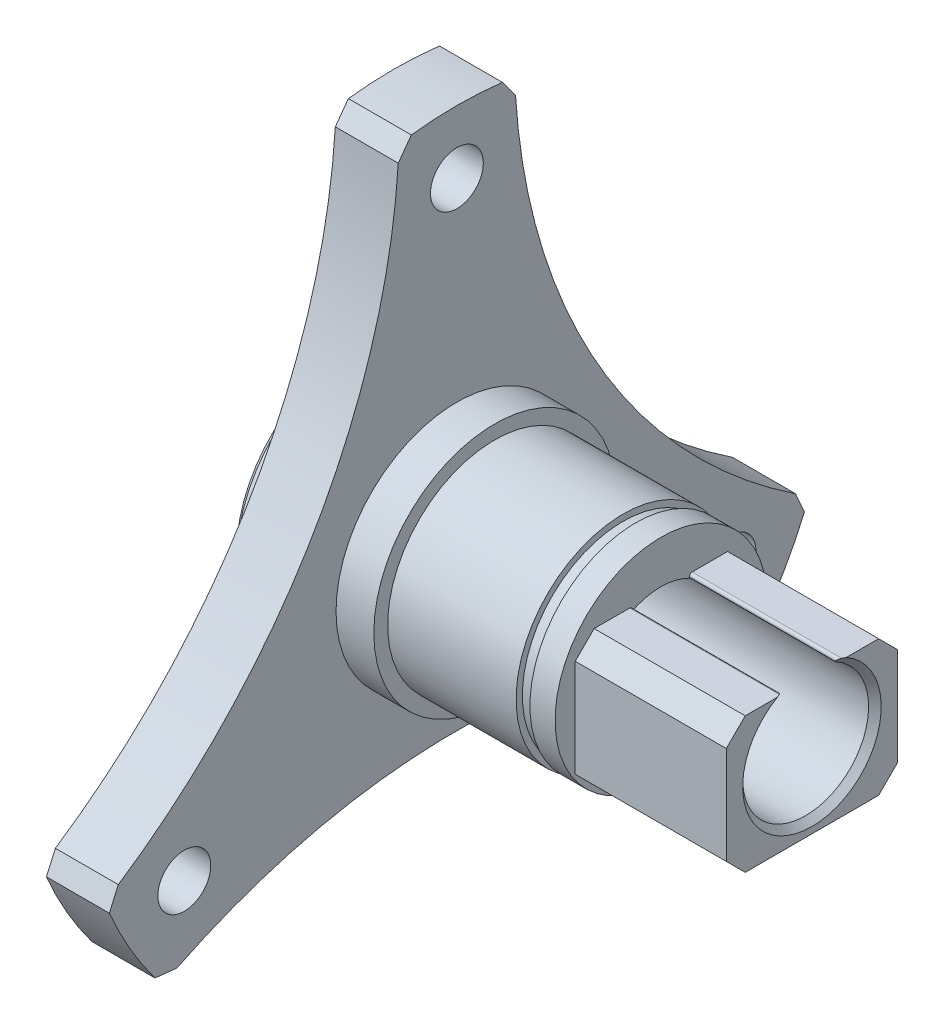
SolidWorks part; units mm, degrees
material "6061-T6 (SS)"
ref_plane "前视基准面" through (0, 0, 0) normal (0, 0, 1) x (1, 0, 0)
ref_plane "上视基准面" through (0, 0, 0) normal (0, 1, 0) x (1, 0, 0)
ref_plane "右视基准面" through (0, 0, 0) normal (1, 0, 0) x (0, 0, -1)
ref_axis "基准轴1" through (48.51, 0, 0) along (-1, 0, 0)
sketch "草图1" plane through (0, 0, 0) normal (0, 0, 1) x (1, 0, 0)
  line L0 (0, 0) -> (0, 10)
  line L2 (3, 10) -> (3, 30)
  line L3 (3, 30) -> (8, 30)
  line L4 (8, 30) -> (8, 9.6)
  line L5 (8, 9.6) -> (11, 9.6)
  line L6 (11, 9.6) -> (11, 8.5)
  line L7 (11, 8.5) -> (21.2, 8.5)
  line L12 (21.2, 8.5) -> (21.2, 8)
  line L13 (21.2, 8) -> (22.2, 8)
  line L14 (22.2, 8) -> (22.2, 8.4)
  line L15 (22.2, 8.4) -> (24.2, 8.4)
  line L16 (24.2, 8.4) -> (24.2, 0)
  line L19 (24.2, 0) -> (0, 0)
  line L21 (0, 10) -> (3, 10)
  dimension "D1" = 8.5
  dimension "D2" = 9.6
  dimension "D7" = 10.2
  dimension "D8" = 3
  dimension "D9" = 5
  dimension "D10" = 30
  dimension "D11" = 10
  dimension "D13" = 3
  dimension "D16" = 8
  dimension "D17" = 1
  dimension "D18" = 8.4
  dimension "D19" = 2
revolve "旋转1" add sketch "草图1" angle 360 about L19
sketch "草图2" plane through (24.2, 0, 0) normal (1, 0, 0) x (0, 0, -1)
  circle A0 centre (0, 0) radius 5
  dimension "D1" = 10
extrude "切除-拉伸1" cut sketch "草图2" against normal through all
sketch "草图3" plane through (0, 0, 0) normal (-1, 0, 0) x (0, 0, 1)
  circle A0 centre (0, 0) radius 8
  dimension "D1" = 16
extrude "切除-拉伸2" cut sketch "草图3" against normal blind 8
chamfer "倒角1" distance 3 angle 30 1 edges at (8, 0, 5) first distance on face at (8, 0, 8)
sketch "草图5" plane through (3, 0, 0) normal (-1, 0, 0) x (0, 0, 1)
  circle A0 centre (0, 0) radius 25 construction
  circle A1 centre (0, 25) radius 2.5
  circle A2 centre (21.6506, -12.5) radius 2.5
  circle A3 centre (-21.6506, -12.5) radius 2.5
  point P12 (0, 0)
  dimension "D1" = 50
  dimension "D2" = 3
  dimension "D3" = 5
hole_wizard "M5 螺纹孔1" positions "3D草图1" profile "草图6" tap size "M5" standard "GB" end condition through all
sketch3d "3D草图1"
  point P0 (3, 25, 0)
  point P3 (3, -12.5, 21.6506)
  point P6 (3, -12.5, -21.6506)
sketch "草图6" plane through (3, 25, 0) normal (0, 1, 0) x (0, 0, 1)
  line L0 (0, 0) -> (0, 21.2)
  line L1 (0, 21.2) -> (2.1, 21.2)
  line L2 (2.1, 21.2) -> (2.1, 0)
  line L5 (2.1, 0) -> (0, 0)
  line L11 (0, -6.35) -> (0, 107.95) construction
  dimension "通孔螺纹孔钻头直径" = 4.2
  dimension "通孔螺纹孔钻头深度" = 21.2
cosmetic thread "孔螺蚊线1" parameters "D2"=5
cosmetic thread "孔螺蚊线2" parameters "D2"=5
cosmetic thread "孔螺蚊线3" parameters "D2"=5
sketch "草图4" plane through (3, 0, 0) normal (-1, 0, 0) x (0, 0, 1)
  line L0 (0, 0) -> (0, -63) construction
  arc A0 (-27.7102, -21.381) -> (27.7102, -21.381) centre (0, 0) ccw
  arc A1 (27.7102, -21.381) -> (-27.7102, -21.381) centre (0, -63) ccw
  dimension "D1" = 70
  dimension "D3" = 100
  dimension "D2" = 63
extrude "切除-拉伸3" cut sketch "草图4" against normal through all
pattern_circular "阵列(圆周)1" count 3 over 360 about axis through (48.51, 0, 0) along (-1, 0, 0) of "切除-拉伸3"
chamfer "倒角2" distance 1 angle 45 6 edges at (5.5, 29.6462, -4.594) (5.5, 29.6462, 4.594) (5.5, -10.8446, 27.9713) (5.5, -18.8016, 23.3773) (5.5, -18.8016, -23.3773) (5.5, -10.8446, -27.9713) first distance on face at (5.5, 29.8231, 0) first distance on face at (5.5, -14.9115, 25.8275) first distance on face at (5.5, -14.9115, -25.8275)
chamfer "倒角4" distance 0.5 angle 45 1 edges at (0, 0, -10)
sketch "草图7" plane through (24.2, 0, 0) normal (1, 0, 0) x (0, 0, -1)
  line L0 (0, 0) -> (0, 2.7252) construction
  line L1 (-6.8, -6) -> (6.8, -6)
  line L2 (-6.8, -6) -> (-6.8, 4.7697)
  line L3 (-6.8, 4.7697) -> (-1.5, 4.7697)
  line L4 (6.8, -6) -> (6.8, 4.7697)
  line L5 (1.5, 4.7697) -> (6.8, 4.7697)
  arc A0 (-1.5, 4.7697) -> (1.5, 4.7697) centre (0, 0) ccw
  dimension "D1" = 10
  dimension "D2" = 13.6
  dimension "D3" = 6
  dimension "D4" = 3
extrude "凸台-拉伸1" add sketch "草图7" along normal blind 12
chamfer "倒角5" distance 1.5 angle 45 4 edges at (30.2, -6, -6.8) (30.2, -6, 6.8) (30.2, 4.7697, -6.8) (30.2, 4.7697, 6.8)
chamfer "倒角6" distance 0.5 angle 45 1 edges at (36.2, -5, 0)
fillet "圆角1" radius 0.2 2 edges at (29.95, 4.7697, 1.5) (29.95, 4.7697, -1.5)
